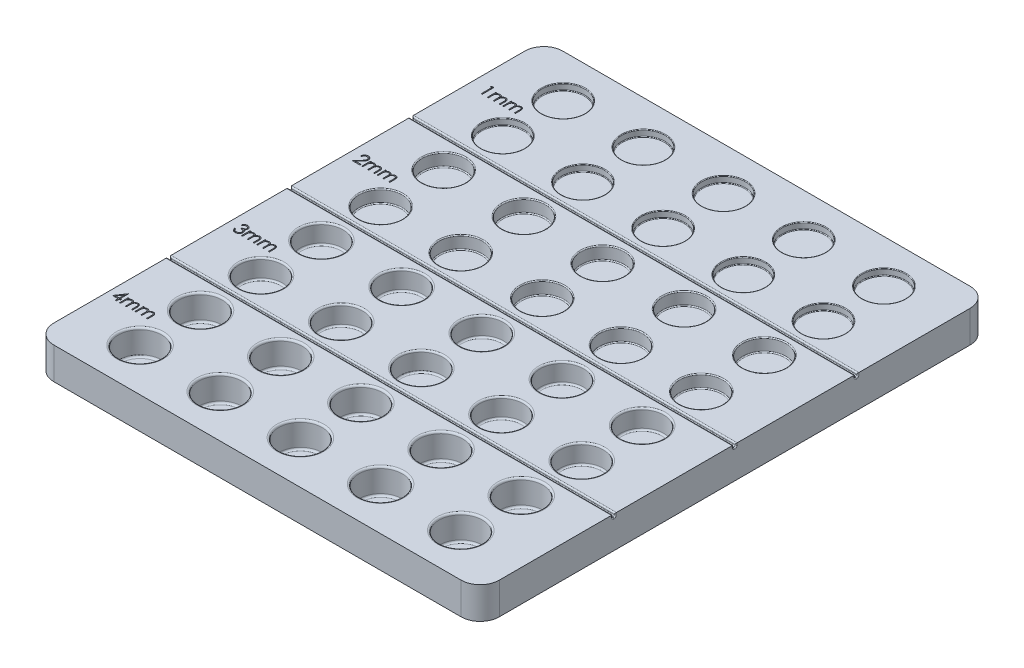
SolidWorks part; units mm, degrees
ref_plane "Front Plane" through (0, 0, 0) normal (0, 0, 1) x (1, 0, 0)
ref_plane "Top Plane" through (0, 0, 0) normal (0, 1, 0) x (1, 0, 0)
ref_plane "Right Plane" through (0, 0, 0) normal (1, 0, 0) x (0, 0, -1)
sketch "Sketch1" plane through (0, 0, 0) normal (0, 1, 0) x (1, 0, 0)
  line L1 (0, 0) -> (66, 0)
  line L2 (0, 0) -> (0, -76)
  line L3 (0, -76) -> (66, -76)
  line L4 (66, 0) -> (66, -76)
  dimension "D1" = 66
  dimension "D2" = 76
extrude "Boss-Extrude1" add sketch "Sketch1" along normal blind 5
ref_plane "Plane1" through (0, 5, 0) normal (0, 1, 0) x (1, 0, 0)
sketch "Sketch5" plane through (0, 5, 0) normal (0, 1, 0) x (1, 0, 0)
  line L0 (66, 0) -> (66, -19)
  line L2 (0, 0) -> (0, -76) construction
  line L4 (0, -38.2) -> (0, -37.8)
  line L9 (66, -19.2) -> (66, -18.8)
  line L11 (0, -19.2) -> (0, -18.8)
  circle A0 centre (33, -4.75) radius 3.4
  circle A1 centre (20.4, -4.75) radius 3.4
  circle A2 centre (7.8, -4.75) radius 3.4
  circle A3 centre (45.6, -4.75) radius 3.4
  circle A4 centre (58.2, -4.75) radius 3.4
  circle A5 centre (58.2, -14.25) radius 3.4
  circle A6 centre (45.6, -14.25) radius 3.4
  circle A7 centre (33, -14.25) radius 3.4
  circle A8 centre (20.4, -14.25) radius 3.4
  circle A9 centre (7.8, -14.25) radius 3.4
  point P92 (0, -38)
  point P100 (66, -19)
  dimension "D1" = 6.8
  dimension "D3" = 6.8
  dimension "D5" = 6.8
extrude "Cut-Extrude3" cut sketch "Sketch5" against normal blind 1 contours A2 | A9 | A1 | A8 | A0 | A7 | A3 | A6 | A5 | A4 region at (33, 5, 4.75) region at (20.4, 5, 4.75) region at (7.8, 5, 4.75) region at (45.6, 5, 4.75) region at (58.2, 5, 14.25) region at (45.6, 5, 14.25) region at (33, 5, 14.25) region at (20.4, 5, 14.25) region at (7.8, 5, 14.25)
sketch "Sketch6" plane through (0, 5, 0) normal (0, 1, 0) x (1, 0, 0)
  line L0 (0, -28.5) -> (66, -28.5)
  line L2 (0, -38) -> (66, -38)
  line L3 (66, -76) -> (66, 0) construction
  line L4 (66, -38) -> (66, 0)
  line L5 (66, 0) -> (66, -19)
  line L6 (66, -19) -> (0, -19)
  line L7 (0, -19) -> (0, -38)
  circle A1 centre (33, -23.75) radius 3.4
  circle A3 centre (20.4062, -23.545) radius 3.4
  circle A4 centre (7.8062, -23.545) radius 3.4
  circle A5 centre (45.5938, -23.545) radius 3.4
  circle A6 centre (58.1938, -23.545) radius 3.4
  circle A7 centre (58.1938, -33.455) radius 3.4
  circle A8 centre (45.5938, -33.455) radius 3.4
  circle A9 centre (33, -33.25) radius 3.4
  circle A10 centre (20.4062, -33.455) radius 3.4
  circle A11 centre (7.8062, -33.455) radius 3.4
  dimension "D1" = 6.8
  dimension "D3" = 6.8
  dimension "D5" = 6.8
extrude "Cut-Extrude5" cut sketch "Sketch6" against normal blind 2 and the other way through all contours A4 | A11 | A3 | A10 | A1 | A9 | A5 | A8 | A6 | A7 region at (33, 5, 23.75) region at (20.4062, 5, 23.545) region at (7.8062, 5, 23.545) region at (45.5938, 5, 23.545) region at (58.1938, 5, 23.545) region at (58.1938, 5, 33.455) region at (45.5938, 5, 33.455) region at (33, 5, 33.25) region at (20.4062, 5, 33.455) region at (7.8062, 5, 33.455)
sketch "Sketch7" plane through (0, 5, 0) normal (0, 1, 0) x (1, 0, 0)
  line L0 (0, 0) -> (0, -76)
  line L1 (0, -76) -> (0, -38)
  line L2 (0, -38) -> (66, -38)
  line L3 (66, -76) -> (66, 0) construction
  line L4 (66, -38) -> (66, -76)
  line L5 (66, -76) -> (66, -57)
  line L6 (66, -57) -> (0, -57)
  line L10 (65.9997, -37.9993) -> (65.9997, -56.9993)
  line L11 (65.9997, -57.1993) -> (65.9997, -56.7993)
  line L12 (-0.0003, -57.1993) -> (-0.0003, -56.7993)
  circle A10 centre (32.9997, -42.7493) radius 3.4
  circle A11 centre (20.3997, -42.7493) radius 3.4
  circle A12 centre (7.7997, -42.7493) radius 3.4
  circle A13 centre (45.5997, -42.7493) radius 3.4
  circle A14 centre (58.1997, -42.7493) radius 3.4
  circle A15 centre (58.1997, -52.2493) radius 3.4
  circle A16 centre (45.5997, -52.2493) radius 3.4
  circle A17 centre (32.9997, -52.2493) radius 3.4
  circle A18 centre (20.3997, -52.2493) radius 3.4
  circle A19 centre (7.7997, -52.2493) radius 3.4
  point P4 (0, 0)
  point P65 (65.9997, -56.9993)
  dimension "D4" = 6.8
  dimension "D5" = 6.8
  dimension "D6" = 6.8
extrude "Cut-Extrude6" cut sketch "Sketch7" against normal blind 3 contours A12 | A19 | A11 | A18 | A13 | A16 | A14 | A15 | A10 | A17 region at (20.3997, 5, 42.7493) region at (7.7997, 5, 42.7493) region at (45.5997, 5, 42.7493) region at (58.1997, 5, 42.7493) region at (58.1997, 5, 52.2493) region at (45.5997, 5, 52.2493) region at (20.3997, 5, 52.2493) region at (7.7997, 5, 52.2493)
sketch "Sketch8" plane through (0, 5, 0) normal (0, 1, 0) x (1, 0, 0)
  line L0 (0, 0) -> (0, -76)
  line L1 (0, -76) -> (0, -38)
  line L2 (66, -57) -> (66, -76)
  line L3 (66, -76.2) -> (66, -75.8)
  line L4 (0, -76.2) -> (0, -75.8)
  circle A0 centre (33, -61.75) radius 3.4
  circle A1 centre (20.4, -61.75) radius 3.4
  circle A2 centre (7.8, -61.75) radius 3.4
  circle A3 centre (45.6, -61.75) radius 3.4
  circle A4 centre (58.2, -61.75) radius 3.4
  circle A5 centre (58.2, -71.25) radius 3.4
  circle A6 centre (45.6, -71.25) radius 3.4
  circle A7 centre (33, -71.25) radius 3.4
  circle A8 centre (20.4, -71.25) radius 3.4
  circle A9 centre (7.8, -71.25) radius 3.4
  point P29 (66, -76)
  dimension "D1" = 6.8
  dimension "D2" = 6.8
  dimension "D3" = 6.8
extrude "Cut-Extrude7" cut sketch "Sketch8" against normal blind 4 contours A2 | A1 | A8 | A0 | A7 | A3 | A6 | A4 | A5 | A9 region at (33, 5, 61.75) region at (20.4, 5, 61.75) region at (7.8, 5, 61.75) region at (45.6, 5, 61.75) region at (58.2, 5, 61.75) region at (58.2, 5, 71.25) region at (45.6, 5, 71.25) region at (33, 5, 71.25) region at (20.4, 5, 71.25)
fillet "Fillet2" radius 0.3 20 edges at (20.4, 1, 65.15) (58.2, 5, 74.65) (58.2, 1, 74.65) (58.2, 5, 65.15) (58.2, 1, 65.15) (45.6, 5, 74.65) (45.6, 1, 74.65) (45.6, 5, 65.15) (45.6, 1, 65.15) (20.4, 5, 74.65) (20.4, 1, 74.65) (33, 5, 74.65) (33, 1, 74.65) (33, 5, 65.15) (33, 1, 65.15) (7.8, 5, 67.85) (7.8, 1, 67.85) (7.8, 5, 65.15) (7.8, 1, 65.15) (20.4, 5, 65.15)
fillet "Fillet3" radius 0.25 20 edges at (45.5997, 5, 55.6493) (45.5997, 2, 55.6493) (58.1997, 5, 55.6493) (58.1997, 2, 55.6493) (58.1997, 5, 46.1493) (58.1997, 2, 46.1493) (45.5997, 5, 46.1493) (45.5997, 2, 46.1493) (32.9997, 5, 48.8493) (32.9997, 2, 48.8493) (32.9997, 5, 46.1493) (32.9997, 2, 46.1493) (20.3997, 5, 55.6493) (20.3997, 2, 55.6493) (20.3997, 5, 46.1493) (20.3997, 2, 46.1493) (7.7997, 5, 55.6493) (7.7997, 2, 55.6493) (7.7997, 5, 46.1493) (7.7997, 2, 46.1493)
fillet "Fillet4" radius 0.15 20 edges at (58.1938, 3, 36.855) (58.1938, 5, 36.855) (58.1938, 3, 26.945) (58.1938, 5, 26.945) (45.5938, 3, 36.855) (45.5938, 5, 36.855) (45.5938, 3, 26.945) (45.5938, 5, 26.945) (33, 3, 36.65) (33, 5, 36.65) (33, 3, 27.15) (33, 5, 27.15) (20.4062, 3, 36.855) (20.4062, 5, 36.855) (20.4062, 3, 26.945) (20.4062, 5, 26.945) (7.8062, 3, 36.855) (7.8062, 5, 36.855) (7.8062, 3, 26.945) (7.8062, 5, 26.945)
fillet "Fillet5" radius 0.1 20 edges at (7.8, 5, 17.65) (7.8, 4, 17.65) (7.8, 5, 8.15) (7.8, 4, 8.15) (20.4, 5, 17.65) (20.4, 4, 17.65) (20.4, 5, 8.15) (20.4, 4, 8.15) (33, 5, 17.65) (33, 4, 17.65) (33, 5, 8.15) (33, 4, 8.15) (45.6, 5, 17.65) (45.6, 4, 17.65) (45.6, 5, 8.15) (45.6, 4, 8.15) (58.2, 5, 17.65) (58.2, 4, 17.65) (58.2, 5, 1.35) (58.2, 4, 1.35)
sketch "Sketch9" plane through (0, 0, 0) normal (0, 1, 0) x (1, 0, 0)
  line L1 (0, 0) -> (66, 0)
  line L2 (0, 0) -> (0, -76)
  line L3 (0, -76) -> (66, -76)
  line L4 (66, 0) -> (66, -76)
  line L9 (-2, 2) -> (68, 2)
  line L10 (-2, 2) -> (-2, -78)
  line L11 (-2, -78) -> (68, -78)
  line L12 (68, 2) -> (68, -78)
  dimension "D5" = 80
extrude "Boss-Extrude2" add sketch "Sketch9" along normal blind 5
sketch "Sketch10" plane through (0, 0, 0) normal (0, 1, 0) x (1, 0, 0)
  line L0 (-2, 2) -> (-2, -78)
  line L1 (-2, -78) -> (-2, -38)
  line L2 (58.2, -17.75) -> (58.1938, -19.995)
  line L3 (68, -78) -> (68, 2) construction
  line L4 (68, -38.2) -> (68, -37.8)
  line L5 (58.1969, -18.8725) -> (68, -18.8725)
  line L6 (68, -57.1747) -> (68, -56.7747)
  line L7 (68, -37.8) -> (-2, -37.8)
  line L8 (68, -57.1747) -> (-2, -57.1747)
  line L9 (68, -57.1747) -> (68, -56.7747)
  line L10 (68, -56.7747) -> (-2, -56.7747)
  line L11 (-2, -57.1747) -> (-2, -56.7747)
  line L12 (68, -37.8) -> (68, -38.2)
  line L13 (68, -38.2) -> (-2, -38.2)
  line L14 (-2, -37.8) -> (-2, -38.2)
  line L15 (68, -19.0725) -> (68, -18.6725)
  line L17 (68, -19.0725) -> (-2, -19.0725)
  line L18 (68, -19.0725) -> (68, -18.6725)
  line L19 (68, -18.6725) -> (-2, -18.6725)
  line L20 (-2, -19.0725) -> (-2, -18.6725)
  circle A2 centre (58.2, -14.25) radius 3.5 construction
  circle A3 centre (58.1938, -23.545) radius 3.55 construction
  point P11 (68, -38)
  point P19 (68, -56.9747)
  point P30 (68, -18.8725)
  dimension "D1" = 0.4
  dimension "D2" = 0.4
  dimension "D3" = 0.4
sketch "Sketch11" plane through (0, 5, 0) normal (0, 1, 0) x (1, 0, 0)
  line L1 (-2, -18.6725) -> (68, -18.6725)
  line L2 (-2, -18.6725) -> (-2, -19.0725)
  line L3 (-2, -19.0725) -> (68, -19.0725)
  line L4 (68, -18.6725) -> (68, -19.0725)
  line L5 (68, -37.8) -> (-2, -37.8)
  line L6 (68, -37.8) -> (68, -38.2)
  line L7 (68, -38.2) -> (-2, -38.2)
  line L8 (-2, -37.8) -> (-2, -38.2)
  line L9 (-2, -56.7747) -> (68, -56.7747)
  line L10 (-2, -56.7747) -> (-2, -57.1747)
  line L11 (-2, -57.1747) -> (68, -57.1747)
  line L12 (68, -56.7747) -> (68, -57.1747)
extrude "Cut-Extrude13" cut sketch "Sketch11" against normal blind 0.5
fillet "Fillet7" radius 0.2 24 edges at (-2, 4.75, 57.1747) (33, 4.5, 57.1747) (68, 4.75, 57.1747) (33, 5, 57.1747) (68, 4.75, 56.7747) (33, 4.5, 56.7747) (-2, 4.75, 56.7747) (33, 5, 56.7747) (-2, 4.75, 38.2) (33, 4.5, 38.2) (68, 4.75, 38.2) (33, 5, 38.2) (68, 4.75, 37.8) (33, 4.5, 37.8) (-2, 4.75, 37.8) (33, 5, 37.8) (-2, 4.75, 19.0725) (33, 4.5, 19.0725) (68, 4.75, 19.0725) (33, 5, 19.0725) (68, 4.75, 18.6725) (33, 4.5, 18.6725) (-2, 4.75, 18.6725) (33, 5, 18.6725)
sketch "Sketch12" plane through (0, 5, 0) normal (0, 1, 0) x (1, 0, 0)
  text T0 "1mm" font "Century Gothic" height in points 7
  text T1 "2mm" font "Century Gothic" height in points 7
  text T2 "3mm\r\n" font "Century Gothic" height in points 7
  text T3 "4mm" font "Century Gothic" height in points 7
extrude "Cut-Extrude14" cut sketch "Sketch12" against normal blind 0.5
fillet "Fillet8" radius 3 4 edges at (68, 2.5, -2) (68, 2.5, 78) (-2, 2.5, 78) (-2, 2.5, -2)
